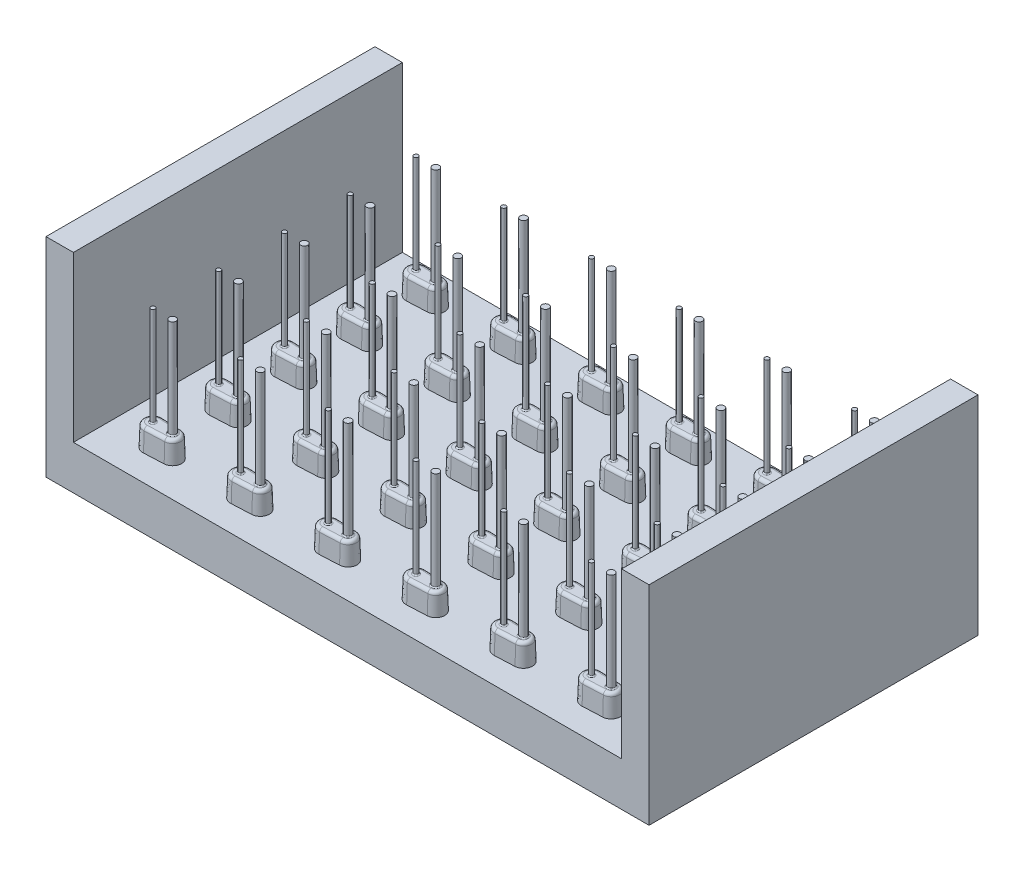
SolidWorks part; units mm, degrees
ref_plane "Front Plane" through (0, 0, 0) normal (0, 0, 1) x (1, 0, 0)
ref_plane "Top Plane" through (0, 0, 0) normal (0, 1, 0) x (1, 0, 0)
ref_plane "Right Plane" through (0, 0, 0) normal (1, 0, 0) x (0, 0, -1)
sketch "Sketch1" plane through (0, 0, 0) normal (0, 1, 0) x (1, 0, 0)
  line L0 (-27.5, 0) -> (27.5, 0) construction
  line L1 (-27.5, 15) -> (27.5, 15)
  line L2 (-27.5, 15) -> (-27.5, -15)
  line L3 (-27.5, -15) -> (27.5, -15)
  line L4 (27.5, 15) -> (27.5, -15)
  line L5 (0, 15) -> (0, -15) construction
  point P4 (0, 15)
  point P5 (-27.5, 0)
  point P10 (0, 0)
  dimension "D1" = 55
  dimension "D2" = 30
extrude "Base" add sketch "Sketch1" along normal blind 4
sketch "Sketch2" plane through (0, 4, 0) normal (0, 1, 0) x (-1, 0, 0)
  line L0 (-27.5, -15) -> (27.5, -15) construction
  line L1 (27.5, 15) -> (25, 15)
  line L2 (27.5, 15) -> (27.5, -15)
  line L3 (27.5, -15) -> (25, -15)
  line L4 (25, 15) -> (25, -15)
  line L6 (-27.5, 15) -> (-25, 15)
  line L7 (-27.5, 15) -> (-27.5, -15)
  line L8 (-27.5, -15) -> (-25, -15)
  line L9 (-25, 15) -> (-25, -15)
  dimension "D1" = 2.5
  dimension "D2" = 2.5
extrude "Walls" add sketch "Sketch2" along normal blind 15
sketch "Sketch3" plane through (0, 4, 0) normal (0, 1, 0) x (-1, 0, 0)
  line L1 (25, 15) -> (25, -15) construction
  line L2 (22, 12) -> (18.2, 12) construction
  line L3 (25, 15) -> (-25, 15) construction
  line L5 (21.9999, 11.1973) -> (18.2001, 11.2973)
  line L6 (18.2, 11.2974) -> (18.2, 12.8972)
  line L7 (18.2001, 12.8973) -> (21.9999, 12.9973)
  line L8 (22, 12.9972) -> (22, 11.1974)
  arc A0 (21.9999, 11.1973) -> (22, 11.1974) centre (21.9999, 11.1974) ccw
  arc A1 (18.2, 11.2974) -> (18.2001, 11.2973) centre (18.2001, 11.2974) ccw
  arc A2 (18.2001, 12.8973) -> (18.2, 12.8972) centre (18.2001, 12.8972) ccw
  arc A3 (22, 12.9972) -> (21.9999, 12.9973) centre (21.9999, 12.9972) ccw
  point P6 (22, 12.9)
  point P9 (22, 11.1973)
  point P13 (18.2, 11.2973)
  point P17 (18.2, 12.8973)
  point P22 (22, 12.9973)
  dimension "D3" = 3
  dimension "D2" = 0.0001
  dimension "D1" = 1.8
  dimension "D4" = 3
  dimension "D5" = 1.6
sketch "screw_post_sketch" plane through (0, 4, 0) normal (0, 1, 0) x (-1, 0, 0)
  line L0 (22, 11.75) -> (18.197, 11.75) construction
  line L2 (25, 15) -> (25, -15) construction
  line L3 (25, 15) -> (-25, 15) construction
  circle A0 centre (21, 11.75) radius 0.2
  dimension "D1" = 4
  dimension "D2" = 3.25
  dimension "D3" = 0.4
extrude "screw_post" add sketch "screw_post_sketch" along normal blind 11
sketch "23_Ga_post_sletch" plane through (0, 4, 0) normal (0, 1, 0) x (-1, 0, 0)
  line L0 (21, 11.75) -> (12.8355, 11.75) construction
  circle A0 centre (19.2, 11.75) radius 0.315
  circle A2 centre (21, 11.75) radius 0.2 construction
  circle A3 centre (21, 11.75) radius 0.2 construction
  dimension "D1" = 1.8
  dimension "D2" = 0.63
extrude "23_Ga_post" add sketch "23_Ga_post_sletch" along normal blind 11
sketch "Sketch4" plane through (0, 4, 0) normal (0, 1, 0) x (-1, 0, 0)
  line L0 (20.9575, 12.649) -> (19.1615, 12.5641)
  line L1 (20.9575, 10.851) -> (19.1615, 10.9359)
  circle A5 centre (19.2, 11.75) radius 0.815
  arc A6 (19.1615, 12.5641) -> (19.1615, 10.9359) centre (19.2, 11.75) ccw
  circle A8 centre (21, 11.75) radius 0.9
  arc A9 (20.9575, 10.851) -> (20.9575, 12.649) centre (21, 11.75) ccw
  dimension "D1" = 0.5
  dimension "D2" = 0.7
extrude "Top_piece_plastic_part" add sketch "Sketch4" along normal blind 2 draft 2
fillet "Top_piece_filet" radius 0.3 4 edges at (-18.4548, 6, 11.75) (-20.0628, 6, 10.9632) (-21.8302, 6, 11.75) (-20.0628, 6, 12.5368)
fillet "Post_filet" radius 0.1 2 edges at (-21, 6, 11.95) (-19.2, 6, 12.065)
pattern_linear "top_piece_pattern" count 5 spacing 6 along (0, 0, -1) count 6 spacing 8 along (1, 0, 0) of "23_Ga_post", "screw_post", "Top_piece_plastic_part", "Top_piece_filet", "Post_filet"
sketch "Sketch6" plane through (0, 4, 0) normal (0, 1, 0) x (-1, 0, 0)
  line L1 (-24.0563, -12.4156) -> (-24.0563, 8.77)
sketch "Sketch5" plane through (0, 4, 0) normal (0, 1, 0) x (-1, 0, 0)
  text T0 "<b>yamajun v1.0 125u</b>" font "Century Gothic" height 1.5
extrude "Extrude1" add sketch "Sketch5" along normal blind 0.25
